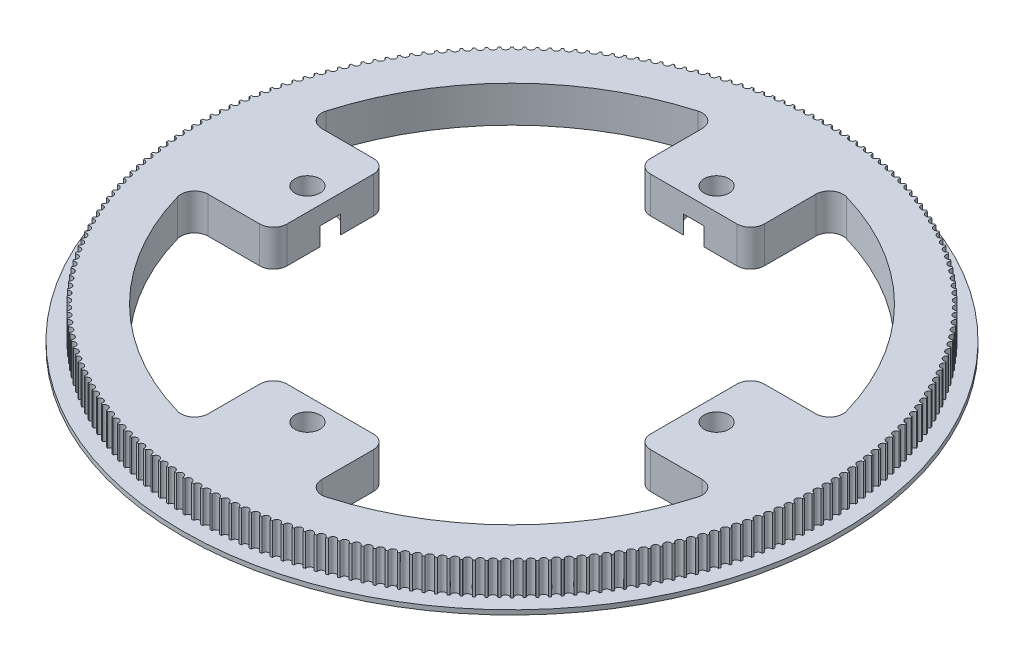
SolidWorks part; units mm, degrees
material "ABS"
ref_plane "Front Plane" through (0, 0, 0) normal (0, 0, 1) x (1, 0, 0)
ref_plane "Top Plane" through (0, 0, 0) normal (0, 1, 0) x (1, 0, 0)
ref_plane "Right Plane" through (0, 0, 0) normal (1, 0, 0) x (0, 0, -1)
sketch "Sketch1" plane through (0, 0, 0) normal (0, 1, 0) x (1, 0, 0)
  arc A0 (-0.76, 69.2508) -> (-1.2179, 69.2443) centre (0, 0) ccw
  arc A1 (-0.76, 69.2508) -> (0.76, 69.2508) centre (0, 69.255) ccw
  arc A2 (1.2179, 69.2443) -> (2.7372, 69.2009) centre (1.9776, 69.2268) ccw
  arc A3 (3.1947, 69.1813) -> (4.7122, 69.0945) centre (3.9537, 69.1421) ccw
  arc A4 (5.1689, 69.0618) -> (6.6833, 68.9318) centre (5.9265, 69.001) ccw
  arc A5 (7.139, 68.8861) -> (8.649, 68.7128) centre (7.8945, 68.8036) ccw
  arc A6 (9.1032, 68.6541) -> (10.6077, 68.4378) centre (9.856, 68.5501) ccw
  arc A7 (11.0599, 68.3662) -> (12.5577, 68.107) centre (11.8095, 68.2407) ccw
  arc A8 (13.0077, 68.0225) -> (14.4974, 67.7206) centre (13.7534, 67.8756) ccw
  arc A9 (14.9449, 67.6233) -> (16.4253, 67.279) centre (15.686, 67.4552) ccw
  arc A10 (16.8698, 67.1689) -> (18.3399, 66.7825) centre (17.6059, 66.9798) ccw
  arc A11 (18.781, 66.6598) -> (20.2394, 66.2316) centre (19.5114, 66.4497) ccw
  arc A12 (20.6769, 66.0963) -> (22.1225, 65.6266) centre (21.401, 65.8654) ccw
  arc A13 (22.5559, 65.4789) -> (23.9875, 64.9681) centre (23.2731, 65.2274) ccw
  arc A14 (24.4165, 64.8081) -> (25.8329, 64.2566) centre (25.1262, 64.5362) ccw
  arc A15 (26.2572, 64.0844) -> (27.6573, 63.4927) centre (26.9589, 63.7924) ccw
  arc A16 (28.0765, 63.3085) -> (29.4591, 62.6771) centre (28.7696, 62.9966) ccw
  arc A17 (29.8729, 62.4809) -> (31.2369, 61.8103) centre (30.5568, 62.1493) ccw
  arc A18 (31.6449, 61.6024) -> (32.9893, 60.8931) centre (32.319, 61.2514) ccw
  arc A19 (33.3912, 60.6736) -> (34.7147, 59.9262) centre (34.055, 60.3035) ccw
  arc A20 (35.1101, 59.6953) -> (36.4118, 58.9104) centre (35.7631, 59.3065) ccw
  arc A21 (36.8005, 58.6684) -> (38.0792, 57.8466) centre (37.4421, 58.261) ccw
  arc A22 (38.4608, 57.5936) -> (39.7155, 56.7356) centre (39.0905, 57.1681) ccw
  arc A23 (40.0898, 56.4718) -> (41.3195, 55.5784) centre (40.7071, 56.0285) ccw
  arc A24 (41.686, 55.304) -> (42.8897, 54.3758) centre (42.2904, 54.8432) ccw
  arc A25 (43.2483, 54.091) -> (44.425, 53.1289) centre (43.8393, 53.6132) ccw
  arc A26 (44.7753, 52.834) -> (45.924, 51.8386) centre (45.3524, 52.3394) ccw
  arc A27 (46.2658, 51.5338) -> (47.3856, 50.5061) centre (46.8285, 51.023) ccw
  arc A28 (47.7185, 50.1916) -> (48.8085, 49.1323) centre (48.2664, 49.665) ccw
  arc A29 (49.1323, 48.8085) -> (50.1916, 47.7185) centre (49.665, 48.2664) ccw
  arc A30 (50.5061, 47.3856) -> (51.5338, 46.2658) centre (51.023, 46.8285) ccw
  arc A31 (51.8386, 45.924) -> (52.834, 44.7753) centre (52.3394, 45.3524) ccw
  arc A32 (53.1289, 44.425) -> (54.091, 43.2483) centre (53.6132, 43.8393) ccw
  arc A33 (54.3758, 42.8897) -> (55.304, 41.686) centre (54.8432, 42.2904) ccw
  arc A34 (55.5784, 41.3195) -> (56.4718, 40.0898) centre (56.0285, 40.7071) ccw
  arc A35 (56.7356, 39.7155) -> (57.5936, 38.4608) centre (57.1681, 39.0905) ccw
  arc A36 (57.8466, 38.0792) -> (58.6684, 36.8005) centre (58.261, 37.4421) ccw
  arc A37 (58.9104, 36.4118) -> (59.6953, 35.1101) centre (59.3065, 35.7631) ccw
  arc A38 (59.9262, 34.7147) -> (60.6736, 33.3912) centre (60.3035, 34.055) ccw
  arc A39 (60.8931, 32.9893) -> (61.6024, 31.6449) centre (61.2514, 32.319) ccw
  arc A40 (61.8103, 31.2369) -> (62.4809, 29.8729) centre (62.1493, 30.5568) ccw
  arc A41 (62.6771, 29.4591) -> (63.3085, 28.0765) centre (62.9966, 28.7696) ccw
  arc A42 (63.4927, 27.6573) -> (64.0844, 26.2572) centre (63.7924, 26.9589) ccw
  arc A43 (64.2566, 25.8329) -> (64.8081, 24.4165) centre (64.5362, 25.1262) ccw
  arc A44 (64.9681, 23.9875) -> (65.4789, 22.5559) centre (65.2274, 23.2731) ccw
  arc A45 (65.6266, 22.1225) -> (66.0963, 20.6769) centre (65.8654, 21.401) ccw
  arc A46 (66.2316, 20.2394) -> (66.6598, 18.781) centre (66.4497, 19.5114) ccw
  arc A47 (66.7825, 18.3399) -> (67.1689, 16.8698) centre (66.9798, 17.6059) ccw
  arc A48 (67.279, 16.4253) -> (67.6233, 14.9449) centre (67.4552, 15.686) ccw
  arc A49 (67.7206, 14.4974) -> (68.0225, 13.0077) centre (67.8756, 13.7534) ccw
  arc A50 (68.107, 12.5577) -> (68.3662, 11.0599) centre (68.2407, 11.8095) ccw
  arc A51 (68.4378, 10.6077) -> (68.6541, 9.1032) centre (68.5501, 9.856) ccw
  arc A52 (68.7128, 8.649) -> (68.8861, 7.139) centre (68.8036, 7.8945) ccw
  arc A53 (68.9318, 6.6833) -> (69.0618, 5.1689) centre (69.001, 5.9265) ccw
  arc A54 (69.0945, 4.7122) -> (69.1813, 3.1947) centre (69.1421, 3.9537) ccw
  arc A55 (69.2009, 2.7372) -> (69.2443, 1.2179) centre (69.2268, 1.9776) ccw
  arc A56 (69.2508, 0.76) -> (69.2508, -0.76) centre (69.255, 0) ccw
  arc A57 (69.2443, -1.2179) -> (69.2009, -2.7372) centre (69.2268, -1.9776) ccw
  arc A58 (69.1813, -3.1947) -> (69.0945, -4.7122) centre (69.1421, -3.9537) ccw
  arc A59 (69.0618, -5.1689) -> (68.9318, -6.6833) centre (69.001, -5.9265) ccw
  arc A60 (68.8861, -7.139) -> (68.7128, -8.649) centre (68.8036, -7.8945) ccw
  arc A61 (68.6541, -9.1032) -> (68.4378, -10.6077) centre (68.5501, -9.856) ccw
  arc A62 (68.3662, -11.0599) -> (68.107, -12.5577) centre (68.2407, -11.8095) ccw
  arc A63 (68.0225, -13.0077) -> (67.7206, -14.4974) centre (67.8756, -13.7534) ccw
  arc A64 (67.6233, -14.9449) -> (67.279, -16.4253) centre (67.4552, -15.686) ccw
  arc A65 (67.1689, -16.8698) -> (66.7825, -18.3399) centre (66.9798, -17.6059) ccw
  arc A66 (66.6598, -18.781) -> (66.2316, -20.2394) centre (66.4497, -19.5114) ccw
  arc A67 (66.0963, -20.6769) -> (65.6266, -22.1225) centre (65.8654, -21.401) ccw
  arc A68 (65.4789, -22.5559) -> (64.9681, -23.9875) centre (65.2274, -23.2731) ccw
  arc A69 (64.8081, -24.4165) -> (64.2566, -25.8329) centre (64.5362, -25.1262) ccw
  arc A70 (64.0844, -26.2572) -> (63.4927, -27.6573) centre (63.7924, -26.9589) ccw
  arc A71 (63.3085, -28.0765) -> (62.6771, -29.4591) centre (62.9966, -28.7696) ccw
  arc A72 (62.4809, -29.8729) -> (61.8103, -31.2369) centre (62.1493, -30.5568) ccw
  arc A73 (61.6024, -31.6449) -> (60.8931, -32.9893) centre (61.2514, -32.319) ccw
  arc A74 (60.6736, -33.3912) -> (59.9262, -34.7147) centre (60.3035, -34.055) ccw
  arc A75 (59.6953, -35.1101) -> (58.9104, -36.4118) centre (59.3065, -35.7631) ccw
  arc A76 (58.6684, -36.8005) -> (57.8466, -38.0792) centre (58.261, -37.4421) ccw
  arc A77 (57.5936, -38.4608) -> (56.7356, -39.7155) centre (57.1681, -39.0905) ccw
  arc A78 (56.4718, -40.0898) -> (55.5784, -41.3195) centre (56.0285, -40.7071) ccw
  arc A79 (55.304, -41.686) -> (54.3758, -42.8897) centre (54.8432, -42.2904) ccw
  arc A80 (54.091, -43.2483) -> (53.1289, -44.425) centre (53.6132, -43.8393) ccw
  arc A81 (52.834, -44.7753) -> (51.8386, -45.924) centre (52.3394, -45.3524) ccw
  arc A82 (51.5338, -46.2658) -> (50.5061, -47.3856) centre (51.023, -46.8285) ccw
  arc A83 (50.1916, -47.7185) -> (49.1323, -48.8085) centre (49.665, -48.2664) ccw
  arc A84 (48.8085, -49.1323) -> (47.7185, -50.1916) centre (48.2664, -49.665) ccw
  arc A85 (47.3856, -50.5061) -> (46.2658, -51.5338) centre (46.8285, -51.023) ccw
  arc A86 (45.924, -51.8386) -> (44.7753, -52.834) centre (45.3524, -52.3394) ccw
  arc A87 (44.425, -53.1289) -> (43.2483, -54.091) centre (43.8393, -53.6132) ccw
  arc A88 (42.8897, -54.3758) -> (41.686, -55.304) centre (42.2904, -54.8432) ccw
  arc A89 (41.3195, -55.5784) -> (40.0898, -56.4718) centre (40.7071, -56.0285) ccw
  arc A90 (39.7155, -56.7356) -> (38.4608, -57.5936) centre (39.0905, -57.1681) ccw
  arc A91 (38.0792, -57.8466) -> (36.8005, -58.6684) centre (37.4421, -58.261) ccw
  arc A92 (36.4118, -58.9104) -> (35.1101, -59.6953) centre (35.7631, -59.3065) ccw
  arc A93 (34.7147, -59.9262) -> (33.3912, -60.6736) centre (34.055, -60.3035) ccw
  arc A94 (32.9893, -60.8931) -> (31.6449, -61.6024) centre (32.319, -61.2514) ccw
  arc A95 (31.2369, -61.8103) -> (29.8729, -62.4809) centre (30.5568, -62.1493) ccw
  arc A96 (29.4591, -62.6771) -> (28.0765, -63.3085) centre (28.7696, -62.9966) ccw
  arc A97 (27.6573, -63.4927) -> (26.2572, -64.0844) centre (26.9589, -63.7924) ccw
  arc A98 (25.8329, -64.2566) -> (24.4165, -64.8081) centre (25.1262, -64.5362) ccw
  arc A99 (23.9875, -64.9681) -> (22.5559, -65.4789) centre (23.2731, -65.2274) ccw
  arc A100 (22.1225, -65.6266) -> (20.6769, -66.0963) centre (21.401, -65.8654) ccw
  arc A101 (20.2394, -66.2316) -> (18.781, -66.6598) centre (19.5114, -66.4497) ccw
  arc A102 (18.3399, -66.7825) -> (16.8698, -67.1689) centre (17.6059, -66.9798) ccw
  arc A103 (16.4253, -67.279) -> (14.9449, -67.6233) centre (15.686, -67.4552) ccw
  arc A104 (14.4974, -67.7206) -> (13.0077, -68.0225) centre (13.7534, -67.8756) ccw
  arc A105 (12.5577, -68.107) -> (11.0599, -68.3662) centre (11.8095, -68.2407) ccw
  arc A106 (10.6077, -68.4378) -> (9.1032, -68.6541) centre (9.856, -68.5501) ccw
  arc A107 (8.649, -68.7128) -> (7.139, -68.8861) centre (7.8945, -68.8036) ccw
  arc A108 (6.6833, -68.9318) -> (5.1689, -69.0618) centre (5.9265, -69.001) ccw
  arc A109 (4.7122, -69.0945) -> (3.1947, -69.1813) centre (3.9537, -69.1421) ccw
  arc A110 (2.7372, -69.2009) -> (1.2179, -69.2443) centre (1.9776, -69.2268) ccw
  arc A111 (0.76, -69.2508) -> (-0.76, -69.2508) centre (0, -69.255) ccw
  arc A112 (-1.2179, -69.2443) -> (-2.7372, -69.2009) centre (-1.9776, -69.2268) ccw
  arc A113 (-3.1947, -69.1813) -> (-4.7122, -69.0945) centre (-3.9537, -69.1421) ccw
  arc A114 (-5.1689, -69.0618) -> (-6.6833, -68.9318) centre (-5.9265, -69.001) ccw
  arc A115 (-7.139, -68.8861) -> (-8.649, -68.7128) centre (-7.8945, -68.8036) ccw
  arc A116 (-9.1032, -68.6541) -> (-10.6077, -68.4378) centre (-9.856, -68.5501) ccw
  arc A117 (-11.0599, -68.3662) -> (-12.5577, -68.107) centre (-11.8095, -68.2407) ccw
  arc A118 (-13.0077, -68.0225) -> (-14.4974, -67.7206) centre (-13.7534, -67.8756) ccw
  arc A119 (-14.9449, -67.6233) -> (-16.4253, -67.279) centre (-15.686, -67.4552) ccw
  arc A120 (-16.8698, -67.1689) -> (-18.3399, -66.7825) centre (-17.6059, -66.9798) ccw
  arc A121 (-18.781, -66.6598) -> (-20.2394, -66.2316) centre (-19.5114, -66.4497) ccw
  arc A122 (-20.6769, -66.0963) -> (-22.1225, -65.6266) centre (-21.401, -65.8654) ccw
  arc A123 (-22.5559, -65.4789) -> (-23.9875, -64.9681) centre (-23.2731, -65.2274) ccw
  arc A124 (-24.4165, -64.8081) -> (-25.8329, -64.2566) centre (-25.1262, -64.5362) ccw
  arc A125 (-26.2572, -64.0844) -> (-27.6573, -63.4927) centre (-26.9589, -63.7924) ccw
  arc A126 (-28.0765, -63.3085) -> (-29.4591, -62.6771) centre (-28.7696, -62.9966) ccw
  arc A127 (-29.8729, -62.4809) -> (-31.2369, -61.8103) centre (-30.5568, -62.1493) ccw
  arc A128 (-31.6449, -61.6024) -> (-32.9893, -60.8931) centre (-32.319, -61.2514) ccw
  arc A129 (-33.3912, -60.6736) -> (-34.7147, -59.9262) centre (-34.055, -60.3035) ccw
  arc A130 (-35.1101, -59.6953) -> (-36.4118, -58.9104) centre (-35.7631, -59.3065) ccw
  arc A131 (-36.8005, -58.6684) -> (-38.0792, -57.8466) centre (-37.4421, -58.261) ccw
  arc A132 (-38.4608, -57.5936) -> (-39.7155, -56.7356) centre (-39.0905, -57.1681) ccw
  arc A133 (-40.0898, -56.4718) -> (-41.3195, -55.5784) centre (-40.7071, -56.0285) ccw
  arc A134 (-41.686, -55.304) -> (-42.8897, -54.3758) centre (-42.2904, -54.8432) ccw
  arc A135 (-43.2483, -54.091) -> (-44.425, -53.1289) centre (-43.8393, -53.6132) ccw
  arc A136 (-44.7753, -52.834) -> (-45.924, -51.8386) centre (-45.3524, -52.3394) ccw
  arc A137 (-46.2658, -51.5338) -> (-47.3856, -50.5061) centre (-46.8285, -51.023) ccw
  arc A138 (-47.7185, -50.1916) -> (-48.8085, -49.1323) centre (-48.2664, -49.665) ccw
  arc A139 (-49.1323, -48.8085) -> (-50.1916, -47.7185) centre (-49.665, -48.2664) ccw
  arc A140 (-50.5061, -47.3856) -> (-51.5338, -46.2658) centre (-51.023, -46.8285) ccw
  arc A141 (-51.8386, -45.924) -> (-52.834, -44.7753) centre (-52.3394, -45.3524) ccw
  arc A142 (-53.1289, -44.425) -> (-54.091, -43.2483) centre (-53.6132, -43.8393) ccw
  arc A143 (-54.3758, -42.8897) -> (-55.304, -41.686) centre (-54.8432, -42.2904) ccw
  arc A144 (-55.5784, -41.3195) -> (-56.4718, -40.0898) centre (-56.0285, -40.7071) ccw
  arc A145 (-56.7356, -39.7155) -> (-57.5936, -38.4608) centre (-57.1681, -39.0905) ccw
  arc A146 (-57.8466, -38.0792) -> (-58.6684, -36.8005) centre (-58.261, -37.4421) ccw
  arc A147 (-58.9104, -36.4118) -> (-59.6953, -35.1101) centre (-59.3065, -35.7631) ccw
  arc A148 (-59.9262, -34.7147) -> (-60.6736, -33.3912) centre (-60.3035, -34.055) ccw
  arc A149 (-60.8931, -32.9893) -> (-61.6024, -31.6449) centre (-61.2514, -32.319) ccw
  arc A150 (-61.8103, -31.2369) -> (-62.4809, -29.8729) centre (-62.1493, -30.5568) ccw
  arc A151 (-62.6771, -29.4591) -> (-63.3085, -28.0765) centre (-62.9966, -28.7696) ccw
  arc A152 (-63.4927, -27.6573) -> (-64.0844, -26.2572) centre (-63.7924, -26.9589) ccw
  arc A153 (-64.2566, -25.8329) -> (-64.8081, -24.4165) centre (-64.5362, -25.1262) ccw
  arc A154 (-64.9681, -23.9875) -> (-65.4789, -22.5559) centre (-65.2274, -23.2731) ccw
  arc A155 (-65.6266, -22.1225) -> (-66.0963, -20.6769) centre (-65.8654, -21.401) ccw
  arc A156 (-66.2316, -20.2394) -> (-66.6598, -18.781) centre (-66.4497, -19.5114) ccw
  arc A157 (-66.7825, -18.3399) -> (-67.1689, -16.8698) centre (-66.9798, -17.6059) ccw
  arc A158 (-67.279, -16.4253) -> (-67.6233, -14.9449) centre (-67.4552, -15.686) ccw
  arc A159 (-67.7206, -14.4974) -> (-68.0225, -13.0077) centre (-67.8756, -13.7534) ccw
  arc A160 (-68.107, -12.5577) -> (-68.3662, -11.0599) centre (-68.2407, -11.8095) ccw
  arc A161 (-68.4378, -10.6077) -> (-68.6541, -9.1032) centre (-68.5501, -9.856) ccw
  arc A162 (-68.7128, -8.649) -> (-68.8861, -7.139) centre (-68.8036, -7.8945) ccw
  arc A163 (-68.9318, -6.6833) -> (-69.0618, -5.1689) centre (-69.001, -5.9265) ccw
  arc A164 (-69.0945, -4.7122) -> (-69.1813, -3.1947) centre (-69.1421, -3.9537) ccw
  arc A165 (-69.2009, -2.7372) -> (-69.2443, -1.2179) centre (-69.2268, -1.9776) ccw
  arc A166 (-69.2508, -0.76) -> (-69.2508, 0.76) centre (-69.255, 0) ccw
  arc A167 (-69.2443, 1.2179) -> (-69.2009, 2.7372) centre (-69.2268, 1.9776) ccw
  arc A168 (-69.1813, 3.1947) -> (-69.0945, 4.7122) centre (-69.1421, 3.9537) ccw
  arc A169 (-69.0618, 5.1689) -> (-68.9318, 6.6833) centre (-69.001, 5.9265) ccw
  arc A170 (-68.8861, 7.139) -> (-68.7128, 8.649) centre (-68.8036, 7.8945) ccw
  arc A171 (-68.6541, 9.1032) -> (-68.4378, 10.6077) centre (-68.5501, 9.856) ccw
  arc A172 (-68.3662, 11.0599) -> (-68.107, 12.5577) centre (-68.2407, 11.8095) ccw
  arc A173 (-68.0225, 13.0077) -> (-67.7206, 14.4974) centre (-67.8756, 13.7534) ccw
  arc A174 (-67.6233, 14.9449) -> (-67.279, 16.4253) centre (-67.4552, 15.686) ccw
  arc A175 (-67.1689, 16.8698) -> (-66.7825, 18.3399) centre (-66.9798, 17.6059) ccw
  arc A176 (-66.6598, 18.781) -> (-66.2316, 20.2394) centre (-66.4497, 19.5114) ccw
  arc A177 (-66.0963, 20.6769) -> (-65.6266, 22.1225) centre (-65.8654, 21.401) ccw
  arc A178 (-65.4789, 22.5559) -> (-64.9681, 23.9875) centre (-65.2274, 23.2731) ccw
  arc A179 (-64.8081, 24.4165) -> (-64.2566, 25.8329) centre (-64.5362, 25.1262) ccw
  arc A180 (-64.0844, 26.2572) -> (-63.4927, 27.6573) centre (-63.7924, 26.9589) ccw
  arc A181 (-63.3085, 28.0765) -> (-62.6771, 29.4591) centre (-62.9966, 28.7696) ccw
  arc A182 (-62.4809, 29.8729) -> (-61.8103, 31.2369) centre (-62.1493, 30.5568) ccw
  arc A183 (-61.6024, 31.6449) -> (-60.8931, 32.9893) centre (-61.2514, 32.319) ccw
  arc A184 (-60.6736, 33.3912) -> (-59.9262, 34.7147) centre (-60.3035, 34.055) ccw
  arc A185 (-59.6953, 35.1101) -> (-58.9104, 36.4118) centre (-59.3065, 35.7631) ccw
  arc A186 (-58.6684, 36.8005) -> (-57.8466, 38.0792) centre (-58.261, 37.4421) ccw
  arc A187 (-57.5936, 38.4608) -> (-56.7356, 39.7155) centre (-57.1681, 39.0905) ccw
  arc A188 (-56.4718, 40.0898) -> (-55.5784, 41.3195) centre (-56.0285, 40.7071) ccw
  arc A189 (-55.304, 41.686) -> (-54.3758, 42.8897) centre (-54.8432, 42.2904) ccw
  arc A190 (-54.091, 43.2483) -> (-53.1289, 44.425) centre (-53.6132, 43.8393) ccw
  arc A191 (-52.834, 44.7753) -> (-51.8386, 45.924) centre (-52.3394, 45.3524) ccw
  arc A192 (-51.5338, 46.2658) -> (-50.5061, 47.3856) centre (-51.023, 46.8285) ccw
  arc A193 (-50.1916, 47.7185) -> (-49.1323, 48.8085) centre (-49.665, 48.2664) ccw
  arc A194 (-48.8085, 49.1323) -> (-47.7185, 50.1916) centre (-48.2664, 49.665) ccw
  arc A195 (-47.3856, 50.5061) -> (-46.2658, 51.5338) centre (-46.8285, 51.023) ccw
  arc A196 (-45.924, 51.8386) -> (-44.7753, 52.834) centre (-45.3524, 52.3394) ccw
  arc A197 (-44.425, 53.1289) -> (-43.2483, 54.091) centre (-43.8393, 53.6132) ccw
  arc A198 (-42.8897, 54.3758) -> (-41.686, 55.304) centre (-42.2904, 54.8432) ccw
  arc A199 (-41.3195, 55.5784) -> (-40.0898, 56.4718) centre (-40.7071, 56.0285) ccw
  arc A200 (-39.7155, 56.7356) -> (-38.4608, 57.5936) centre (-39.0905, 57.1681) ccw
  arc A201 (-38.0792, 57.8466) -> (-36.8005, 58.6684) centre (-37.4421, 58.261) ccw
  arc A202 (-36.4118, 58.9104) -> (-35.1101, 59.6953) centre (-35.7631, 59.3065) ccw
  arc A203 (-34.7147, 59.9262) -> (-33.3912, 60.6736) centre (-34.055, 60.3035) ccw
  arc A204 (-32.9893, 60.8931) -> (-31.6449, 61.6024) centre (-32.319, 61.2514) ccw
  arc A205 (-31.2369, 61.8103) -> (-29.8729, 62.4809) centre (-30.5568, 62.1493) ccw
  arc A206 (-29.4591, 62.6771) -> (-28.0765, 63.3085) centre (-28.7696, 62.9966) ccw
  arc A207 (-27.6573, 63.4927) -> (-26.2572, 64.0844) centre (-26.9589, 63.7924) ccw
  arc A208 (-25.8329, 64.2566) -> (-24.4165, 64.8081) centre (-25.1262, 64.5362) ccw
  arc A209 (-23.9875, 64.9681) -> (-22.5559, 65.4789) centre (-23.2731, 65.2274) ccw
  arc A210 (-22.1225, 65.6266) -> (-20.6769, 66.0963) centre (-21.401, 65.8654) ccw
  arc A211 (-20.2394, 66.2316) -> (-18.781, 66.6598) centre (-19.5114, 66.4497) ccw
  arc A212 (-18.3399, 66.7825) -> (-16.8698, 67.1689) centre (-17.6059, 66.9798) ccw
  arc A213 (-16.4253, 67.279) -> (-14.9449, 67.6233) centre (-15.686, 67.4552) ccw
  arc A214 (-14.4974, 67.7206) -> (-13.0077, 68.0225) centre (-13.7534, 67.8756) ccw
  arc A215 (-12.5577, 68.107) -> (-11.0599, 68.3662) centre (-11.8095, 68.2407) ccw
  arc A216 (-10.6077, 68.4378) -> (-9.1032, 68.6541) centre (-9.856, 68.5501) ccw
  arc A217 (-8.649, 68.7128) -> (-7.139, 68.8861) centre (-7.8945, 68.8036) ccw
  arc A218 (-6.6833, 68.9318) -> (-5.1689, 69.0618) centre (-5.9265, 69.001) ccw
  arc A219 (-4.7122, 69.0945) -> (-3.1947, 69.1813) centre (-3.9537, 69.1421) ccw
  arc A220 (-2.7372, 69.2009) -> (-1.2179, 69.2443) centre (-1.9776, 69.2268) ccw
  arc A221 (1.2179, 69.2443) -> (0.76, 69.2508) centre (0, 0) ccw
  arc A222 (3.1947, 69.1813) -> (2.7372, 69.2009) centre (0, 0) ccw
  arc A223 (5.1689, 69.0618) -> (4.7122, 69.0945) centre (0, 0) ccw
  arc A224 (7.139, 68.8861) -> (6.6833, 68.9318) centre (0, 0) ccw
  arc A225 (9.1032, 68.6541) -> (8.649, 68.7128) centre (0, 0) ccw
  arc A226 (11.0599, 68.3662) -> (10.6077, 68.4378) centre (0, 0) ccw
  arc A227 (13.0077, 68.0225) -> (12.5577, 68.107) centre (0, 0) ccw
  arc A228 (14.9449, 67.6233) -> (14.4974, 67.7206) centre (0, 0) ccw
  arc A229 (16.8698, 67.1689) -> (16.4253, 67.279) centre (0, 0) ccw
  arc A230 (18.781, 66.6598) -> (18.3399, 66.7825) centre (0, 0) ccw
  arc A231 (20.6769, 66.0963) -> (20.2394, 66.2316) centre (0, 0) ccw
  arc A232 (22.5559, 65.4789) -> (22.1225, 65.6266) centre (0, 0) ccw
  arc A233 (24.4165, 64.8081) -> (23.9875, 64.9681) centre (0, 0) ccw
  arc A234 (26.2572, 64.0844) -> (25.8329, 64.2566) centre (0, 0) ccw
  arc A235 (28.0765, 63.3085) -> (27.6573, 63.4927) centre (0, 0) ccw
  arc A236 (29.8729, 62.4809) -> (29.4591, 62.6771) centre (0, 0) ccw
  arc A237 (31.6449, 61.6024) -> (31.2369, 61.8103) centre (0, 0) ccw
  arc A238 (33.3912, 60.6736) -> (32.9893, 60.8931) centre (0, 0) ccw
  arc A239 (35.1101, 59.6953) -> (34.7147, 59.9262) centre (0, 0) ccw
  arc A240 (36.8005, 58.6684) -> (36.4118, 58.9104) centre (0, 0) ccw
  arc A241 (38.4608, 57.5936) -> (38.0792, 57.8466) centre (0, 0) ccw
  arc A242 (40.0898, 56.4718) -> (39.7155, 56.7356) centre (0, 0) ccw
  arc A243 (41.686, 55.304) -> (41.3195, 55.5784) centre (0, 0) ccw
  arc A244 (43.2483, 54.091) -> (42.8897, 54.3758) centre (0, 0) ccw
  arc A245 (44.7753, 52.834) -> (44.425, 53.1289) centre (0, 0) ccw
  arc A246 (46.2658, 51.5338) -> (45.924, 51.8386) centre (0, 0) ccw
  arc A247 (47.7185, 50.1916) -> (47.3856, 50.5061) centre (0, 0) ccw
  arc A248 (49.1323, 48.8085) -> (48.8085, 49.1323) centre (0, 0) ccw
  arc A249 (50.5061, 47.3856) -> (50.1916, 47.7185) centre (0, 0) ccw
  arc A250 (51.8386, 45.924) -> (51.5338, 46.2658) centre (0, 0) ccw
  arc A251 (53.1289, 44.425) -> (52.834, 44.7753) centre (0, 0) ccw
  arc A252 (54.3758, 42.8897) -> (54.091, 43.2483) centre (0, 0) ccw
  arc A253 (55.5784, 41.3195) -> (55.304, 41.686) centre (0, 0) ccw
  arc A254 (56.7356, 39.7155) -> (56.4718, 40.0898) centre (0, 0) ccw
  arc A255 (57.8466, 38.0792) -> (57.5936, 38.4608) centre (0, 0) ccw
  arc A256 (58.9104, 36.4118) -> (58.6684, 36.8005) centre (0, 0) ccw
  arc A257 (59.9262, 34.7147) -> (59.6953, 35.1101) centre (0, 0) ccw
  arc A258 (60.8931, 32.9893) -> (60.6736, 33.3912) centre (0, 0) ccw
  arc A259 (61.8103, 31.2369) -> (61.6024, 31.6449) centre (0, 0) ccw
  arc A260 (62.6771, 29.4591) -> (62.4809, 29.8729) centre (0, 0) ccw
  arc A261 (63.4927, 27.6573) -> (63.3085, 28.0765) centre (0, 0) ccw
  arc A262 (64.2566, 25.8329) -> (64.0844, 26.2572) centre (0, 0) ccw
  arc A263 (64.9681, 23.9875) -> (64.8081, 24.4165) centre (0, 0) ccw
  arc A264 (65.6266, 22.1225) -> (65.4789, 22.5559) centre (0, 0) ccw
  arc A265 (66.2316, 20.2394) -> (66.0963, 20.6769) centre (0, 0) ccw
  arc A266 (66.7825, 18.3399) -> (66.6598, 18.781) centre (0, 0) ccw
  arc A267 (67.279, 16.4253) -> (67.1689, 16.8698) centre (0, 0) ccw
  arc A268 (67.7206, 14.4974) -> (67.6233, 14.9449) centre (0, 0) ccw
  arc A269 (68.107, 12.5577) -> (68.0225, 13.0077) centre (0, 0) ccw
  arc A270 (68.4378, 10.6077) -> (68.3662, 11.0599) centre (0, 0) ccw
  arc A271 (68.7128, 8.649) -> (68.6541, 9.1032) centre (0, 0) ccw
  arc A272 (68.9318, 6.6833) -> (68.8861, 7.139) centre (0, 0) ccw
  arc A273 (69.0945, 4.7122) -> (69.0618, 5.1689) centre (0, 0) ccw
  arc A274 (69.2009, 2.7372) -> (69.1813, 3.1947) centre (0, 0) ccw
  arc A275 (69.2508, 0.76) -> (69.2443, 1.2179) centre (0, 0) ccw
  arc A276 (69.2443, -1.2179) -> (69.2508, -0.76) centre (0, 0) ccw
  arc A277 (69.1813, -3.1947) -> (69.2009, -2.7372) centre (0, 0) ccw
  arc A278 (69.0618, -5.1689) -> (69.0945, -4.7122) centre (0, 0) ccw
  arc A279 (68.8861, -7.139) -> (68.9318, -6.6833) centre (0, 0) ccw
  arc A280 (68.6541, -9.1032) -> (68.7128, -8.649) centre (0, 0) ccw
  arc A281 (68.3662, -11.0599) -> (68.4378, -10.6077) centre (0, 0) ccw
  arc A282 (68.0225, -13.0077) -> (68.107, -12.5577) centre (0, 0) ccw
  arc A283 (67.6233, -14.9449) -> (67.7206, -14.4974) centre (0, 0) ccw
  arc A284 (67.1689, -16.8698) -> (67.279, -16.4253) centre (0, 0) ccw
  arc A285 (66.6598, -18.781) -> (66.7825, -18.3399) centre (0, 0) ccw
  arc A286 (66.0963, -20.6769) -> (66.2316, -20.2394) centre (0, 0) ccw
  arc A287 (65.4789, -22.5559) -> (65.6266, -22.1225) centre (0, 0) ccw
  arc A288 (64.8081, -24.4165) -> (64.9681, -23.9875) centre (0, 0) ccw
  arc A289 (64.0844, -26.2572) -> (64.2566, -25.8329) centre (0, 0) ccw
  arc A290 (63.3085, -28.0765) -> (63.4927, -27.6573) centre (0, 0) ccw
  arc A291 (62.4809, -29.8729) -> (62.6771, -29.4591) centre (0, 0) ccw
  arc A292 (61.6024, -31.6449) -> (61.8103, -31.2369) centre (0, 0) ccw
  arc A293 (60.6736, -33.3912) -> (60.8931, -32.9893) centre (0, 0) ccw
  arc A294 (59.6953, -35.1101) -> (59.9262, -34.7147) centre (0, 0) ccw
  arc A295 (58.6684, -36.8005) -> (58.9104, -36.4118) centre (0, 0) ccw
  arc A296 (57.5936, -38.4608) -> (57.8466, -38.0792) centre (0, 0) ccw
  arc A297 (56.4718, -40.0898) -> (56.7356, -39.7155) centre (0, 0) ccw
  arc A298 (55.304, -41.686) -> (55.5784, -41.3195) centre (0, 0) ccw
  arc A299 (54.091, -43.2483) -> (54.3758, -42.8897) centre (0, 0) ccw
  arc A300 (52.834, -44.7753) -> (53.1289, -44.425) centre (0, 0) ccw
  arc A301 (51.5338, -46.2658) -> (51.8386, -45.924) centre (0, 0) ccw
  arc A302 (50.1916, -47.7185) -> (50.5061, -47.3856) centre (0, 0) ccw
  arc A303 (48.8085, -49.1323) -> (49.1323, -48.8085) centre (0, 0) ccw
  arc A304 (47.3856, -50.5061) -> (47.7185, -50.1916) centre (0, 0) ccw
  arc A305 (45.924, -51.8386) -> (46.2658, -51.5338) centre (0, 0) ccw
  arc A306 (44.425, -53.1289) -> (44.7753, -52.834) centre (0, 0) ccw
  arc A307 (42.8897, -54.3758) -> (43.2483, -54.091) centre (0, 0) ccw
  arc A308 (41.3195, -55.5784) -> (41.686, -55.304) centre (0, 0) ccw
  arc A309 (39.7155, -56.7356) -> (40.0898, -56.4718) centre (0, 0) ccw
  arc A310 (38.0792, -57.8466) -> (38.4608, -57.5936) centre (0, 0) ccw
  arc A311 (36.4118, -58.9104) -> (36.8005, -58.6684) centre (0, 0) ccw
  arc A312 (34.7147, -59.9262) -> (35.1101, -59.6953) centre (0, 0) ccw
  arc A313 (32.9893, -60.8931) -> (33.3912, -60.6736) centre (0, 0) ccw
  arc A314 (31.2369, -61.8103) -> (31.6449, -61.6024) centre (0, 0) ccw
  arc A315 (29.4591, -62.6771) -> (29.8729, -62.4809) centre (0, 0) ccw
  arc A316 (27.6573, -63.4927) -> (28.0765, -63.3085) centre (0, 0) ccw
  arc A317 (23.9875, -64.9681) -> (24.4165, -64.8081) centre (0, 0) ccw
  arc A318 (25.8329, -64.2566) -> (26.2572, -64.0844) centre (0, 0) ccw
  arc A319 (22.1225, -65.6266) -> (22.5559, -65.4789) centre (0, 0) ccw
  arc A320 (20.2394, -66.2316) -> (20.6769, -66.0963) centre (0, 0) ccw
  arc A321 (18.3399, -66.7825) -> (18.781, -66.6598) centre (0, 0) ccw
  arc A322 (16.4253, -67.279) -> (16.8698, -67.1689) centre (0, 0) ccw
  arc A323 (14.4974, -67.7206) -> (14.9449, -67.6233) centre (0, 0) ccw
  arc A324 (12.5577, -68.107) -> (13.0077, -68.0225) centre (0, 0) ccw
  arc A325 (10.6077, -68.4378) -> (11.0599, -68.3662) centre (0, 0) ccw
  arc A326 (8.649, -68.7128) -> (9.1032, -68.6541) centre (0, 0) ccw
  arc A327 (6.6833, -68.9318) -> (7.139, -68.8861) centre (0, 0) ccw
  arc A328 (4.7122, -69.0945) -> (5.1689, -69.0618) centre (0, 0) ccw
  arc A329 (2.7372, -69.2009) -> (3.1947, -69.1813) centre (0, 0) ccw
  arc A330 (0.76, -69.2508) -> (1.2179, -69.2443) centre (0, 0) ccw
  arc A331 (-1.2179, -69.2443) -> (-0.76, -69.2508) centre (0, 0) ccw
  arc A332 (-3.1947, -69.1813) -> (-2.7372, -69.2009) centre (0, 0) ccw
  arc A333 (-5.1689, -69.0618) -> (-4.7122, -69.0945) centre (0, 0) ccw
  arc A334 (-7.139, -68.8861) -> (-6.6833, -68.9318) centre (0, 0) ccw
  arc A335 (-9.1032, -68.6541) -> (-8.649, -68.7128) centre (0, 0) ccw
  arc A336 (-11.0599, -68.3662) -> (-10.6077, -68.4378) centre (0, 0) ccw
  arc A337 (-13.0077, -68.0225) -> (-12.5577, -68.107) centre (0, 0) ccw
  arc A338 (-14.9449, -67.6233) -> (-14.4974, -67.7206) centre (0, 0) ccw
  arc A339 (-16.8698, -67.1689) -> (-16.4253, -67.279) centre (0, 0) ccw
  arc A340 (-18.781, -66.6598) -> (-18.3399, -66.7825) centre (0, 0) ccw
  arc A341 (-20.6769, -66.0963) -> (-20.2394, -66.2316) centre (0, 0) ccw
  arc A342 (-22.5559, -65.4789) -> (-22.1225, -65.6266) centre (0, 0) ccw
  arc A343 (-24.4165, -64.8081) -> (-23.9875, -64.9681) centre (0, 0) ccw
  arc A344 (-26.2572, -64.0844) -> (-25.8329, -64.2566) centre (0, 0) ccw
  arc A345 (-28.0765, -63.3085) -> (-27.6573, -63.4927) centre (0, 0) ccw
  arc A346 (-29.8729, -62.4809) -> (-29.4591, -62.6771) centre (0, 0) ccw
  arc A347 (-31.6449, -61.6024) -> (-31.2369, -61.8103) centre (0, 0) ccw
  arc A348 (-33.3912, -60.6736) -> (-32.9893, -60.8931) centre (0, 0) ccw
  arc A349 (-35.1101, -59.6953) -> (-34.7147, -59.9262) centre (0, 0) ccw
  arc A350 (-36.8005, -58.6684) -> (-36.4118, -58.9104) centre (0, 0) ccw
  arc A351 (-38.4608, -57.5936) -> (-38.0792, -57.8466) centre (0, 0) ccw
  arc A352 (-40.0898, -56.4718) -> (-39.7155, -56.7356) centre (0, 0) ccw
  arc A353 (-41.686, -55.304) -> (-41.3195, -55.5784) centre (0, 0) ccw
  arc A354 (-43.2483, -54.091) -> (-42.8897, -54.3758) centre (0, 0) ccw
  arc A355 (-44.7753, -52.834) -> (-44.425, -53.1289) centre (0, 0) ccw
  arc A356 (-46.2658, -51.5338) -> (-45.924, -51.8386) centre (0, 0) ccw
  arc A357 (-47.7185, -50.1916) -> (-47.3856, -50.5061) centre (0, 0) ccw
  arc A358 (-49.1323, -48.8085) -> (-48.8085, -49.1323) centre (0, 0) ccw
  arc A359 (-50.5061, -47.3856) -> (-50.1916, -47.7185) centre (0, 0) ccw
  arc A360 (-51.8386, -45.924) -> (-51.5338, -46.2658) centre (0, 0) ccw
  arc A361 (-53.1289, -44.425) -> (-52.834, -44.7753) centre (0, 0) ccw
  arc A362 (-54.3758, -42.8897) -> (-54.091, -43.2483) centre (0, 0) ccw
  arc A363 (-55.5784, -41.3195) -> (-55.304, -41.686) centre (0, 0) ccw
  arc A364 (-56.7356, -39.7155) -> (-56.4718, -40.0898) centre (0, 0) ccw
  arc A365 (-57.8466, -38.0792) -> (-57.5936, -38.4608) centre (0, 0) ccw
  arc A366 (-58.9104, -36.4118) -> (-58.6684, -36.8005) centre (0, 0) ccw
  arc A367 (-59.9262, -34.7147) -> (-59.6953, -35.1101) centre (0, 0) ccw
  arc A368 (-60.8931, -32.9893) -> (-60.6736, -33.3912) centre (0, 0) ccw
  arc A369 (-61.8103, -31.2369) -> (-61.6024, -31.6449) centre (0, 0) ccw
  arc A370 (-62.6771, -29.4591) -> (-62.4809, -29.8729) centre (0, 0) ccw
  arc A371 (-63.4927, -27.6573) -> (-63.3085, -28.0765) centre (0, 0) ccw
  arc A372 (-64.2566, -25.8329) -> (-64.0844, -26.2572) centre (0, 0) ccw
  arc A373 (-64.9681, -23.9875) -> (-64.8081, -24.4165) centre (0, 0) ccw
  arc A374 (-65.6266, -22.1225) -> (-65.4789, -22.5559) centre (0, 0) ccw
  arc A375 (-66.2316, -20.2394) -> (-66.0963, -20.6769) centre (0, 0) ccw
  arc A376 (-66.7825, -18.3399) -> (-66.6598, -18.781) centre (0, 0) ccw
  arc A377 (-67.279, -16.4253) -> (-67.1689, -16.8698) centre (0, 0) ccw
  arc A378 (-67.7206, -14.4974) -> (-67.6233, -14.9449) centre (0, 0) ccw
  arc A379 (-68.107, -12.5577) -> (-68.0225, -13.0077) centre (0, 0) ccw
  arc A380 (-68.4378, -10.6077) -> (-68.3662, -11.0599) centre (0, 0) ccw
  arc A381 (-68.7128, -8.649) -> (-68.6541, -9.1032) centre (0, 0) ccw
  arc A382 (-68.9318, -6.6833) -> (-68.8861, -7.139) centre (0, 0) ccw
  arc A383 (-69.0945, -4.7122) -> (-69.0618, -5.1689) centre (0, 0) ccw
  arc A384 (-69.2009, -2.7372) -> (-69.1813, -3.1947) centre (0, 0) ccw
  arc A385 (-69.2508, -0.76) -> (-69.2443, -1.2179) centre (0, 0) ccw
  arc A386 (-69.2443, 1.2179) -> (-69.2508, 0.76) centre (0, 0) ccw
  arc A387 (-69.1813, 3.1947) -> (-69.2009, 2.7372) centre (0, 0) ccw
  arc A388 (-69.0618, 5.1689) -> (-69.0945, 4.7122) centre (0, 0) ccw
  arc A389 (-68.8861, 7.139) -> (-68.9318, 6.6833) centre (0, 0) ccw
  arc A390 (-68.6541, 9.1032) -> (-68.7128, 8.649) centre (0, 0) ccw
  arc A391 (-68.3662, 11.0599) -> (-68.4378, 10.6077) centre (0, 0) ccw
  arc A392 (-68.0225, 13.0077) -> (-68.107, 12.5577) centre (0, 0) ccw
  arc A393 (-67.6233, 14.9449) -> (-67.7206, 14.4974) centre (0, 0) ccw
  arc A394 (-67.1689, 16.8698) -> (-67.279, 16.4253) centre (0, 0) ccw
  arc A395 (-66.6598, 18.781) -> (-66.7825, 18.3399) centre (0, 0) ccw
  arc A396 (-66.0963, 20.6769) -> (-66.2316, 20.2394) centre (0, 0) ccw
  arc A397 (-65.4789, 22.5559) -> (-65.6266, 22.1225) centre (0, 0) ccw
  arc A398 (-64.8081, 24.4165) -> (-64.9681, 23.9875) centre (0, 0) ccw
  arc A399 (-64.0844, 26.2572) -> (-64.2566, 25.8329) centre (0, 0) ccw
  arc A400 (-63.3085, 28.0765) -> (-63.4927, 27.6573) centre (0, 0) ccw
  arc A401 (-62.4809, 29.8729) -> (-62.6771, 29.4591) centre (0, 0) ccw
  arc A402 (-61.6024, 31.6449) -> (-61.8103, 31.2369) centre (0, 0) ccw
  arc A403 (-60.6736, 33.3912) -> (-60.8931, 32.9893) centre (0, 0) ccw
  arc A404 (-59.6953, 35.1101) -> (-59.9262, 34.7147) centre (0, 0) ccw
  arc A405 (-58.6684, 36.8005) -> (-58.9104, 36.4118) centre (0, 0) ccw
  arc A406 (-57.5936, 38.4608) -> (-57.8466, 38.0792) centre (0, 0) ccw
  arc A407 (-56.4718, 40.0898) -> (-56.7356, 39.7155) centre (0, 0) ccw
  arc A408 (-55.304, 41.686) -> (-55.5784, 41.3195) centre (0, 0) ccw
  arc A409 (-54.091, 43.2483) -> (-54.3758, 42.8897) centre (0, 0) ccw
  arc A410 (-52.834, 44.7753) -> (-53.1289, 44.425) centre (0, 0) ccw
  arc A411 (-51.5338, 46.2658) -> (-51.8386, 45.924) centre (0, 0) ccw
  arc A412 (-50.1916, 47.7185) -> (-50.5061, 47.3856) centre (0, 0) ccw
  arc A413 (-48.8085, 49.1323) -> (-49.1323, 48.8085) centre (0, 0) ccw
  arc A414 (-47.3856, 50.5061) -> (-47.7185, 50.1916) centre (0, 0) ccw
  arc A415 (-45.924, 51.8386) -> (-46.2658, 51.5338) centre (0, 0) ccw
  arc A416 (-42.8897, 54.3758) -> (-43.2483, 54.091) centre (0, 0) ccw
  arc A417 (-44.425, 53.1289) -> (-44.7753, 52.834) centre (0, 0) ccw
  arc A418 (-41.3195, 55.5784) -> (-41.686, 55.304) centre (0, 0) ccw
  arc A419 (-39.7155, 56.7356) -> (-40.0898, 56.4718) centre (0, 0) ccw
  arc A420 (-38.0792, 57.8466) -> (-38.4608, 57.5936) centre (0, 0) ccw
  arc A421 (-36.4118, 58.9104) -> (-36.8005, 58.6684) centre (0, 0) ccw
  arc A422 (-34.7147, 59.9262) -> (-35.1101, 59.6953) centre (0, 0) ccw
  arc A423 (-32.9893, 60.8931) -> (-33.3912, 60.6736) centre (0, 0) ccw
  arc A424 (-31.2369, 61.8103) -> (-31.6449, 61.6024) centre (0, 0) ccw
  arc A425 (-29.4591, 62.6771) -> (-29.8729, 62.4809) centre (0, 0) ccw
  arc A426 (-27.6573, 63.4927) -> (-28.0765, 63.3085) centre (0, 0) ccw
  arc A427 (-25.8329, 64.2566) -> (-26.2572, 64.0844) centre (0, 0) ccw
  arc A428 (-23.9875, 64.9681) -> (-24.4165, 64.8081) centre (0, 0) ccw
  arc A429 (-22.1225, 65.6266) -> (-22.5559, 65.4789) centre (0, 0) ccw
  arc A430 (-20.2394, 66.2316) -> (-20.6769, 66.0963) centre (0, 0) ccw
  arc A431 (-18.3399, 66.7825) -> (-18.781, 66.6598) centre (0, 0) ccw
  arc A432 (-16.4253, 67.279) -> (-16.8698, 67.1689) centre (0, 0) ccw
  arc A433 (-14.4974, 67.7206) -> (-14.9449, 67.6233) centre (0, 0) ccw
  arc A434 (-12.5577, 68.107) -> (-13.0077, 68.0225) centre (0, 0) ccw
  arc A435 (-8.649, 68.7128) -> (-9.1032, 68.6541) centre (0, 0) ccw
  arc A436 (-10.6077, 68.4378) -> (-11.0599, 68.3662) centre (0, 0) ccw
  arc A437 (-6.6833, 68.9318) -> (-7.139, 68.8861) centre (0, 0) ccw
  arc A438 (-4.7122, 69.0945) -> (-5.1689, 69.0618) centre (0, 0) ccw
  arc A439 (-2.7372, 69.2009) -> (-3.1947, 69.1813) centre (0, 0) ccw
  point P665 (0, 0)
  dimension "D1" = 138.51
  dimension "D2" = 1.52
  dimension "D3" = 220
extrude "Boss-Extrude1" add sketch "Sketch1" along normal blind 7
sketch "Sketch3" plane through (0, 0, 0) normal (0, -1, 0) x (1, 0, 0)
  circle A0 centre (0, 0) radius 72.5
extrude "Boss-Extrude3" add sketch "Sketch3" along normal blind 1
sketch "Sketch6" plane through (0, 7, 0) normal (0, 1, 0) x (1, 0, 0)
  line L0 (0, 0) -> (0, 50000) construction
  line L5 (-42.4236, 42.4236) -> (42.4292, -42.4292) construction
  line L6 (-42.4264, -42.4264) -> (42.4264, 42.4264) construction
  circle A0 centre (42.4264, 42.4264) radius 2.5
  circle A1 centre (42.4292, -42.4292) radius 2.5
  circle A2 centre (-42.4264, -42.4264) radius 2.5
  circle A3 centre (-42.4236, 42.4236) radius 2.5
  point P0 (0, 0)
  dimension "D3" = 5
  dimension "D1" = 84.85
  dimension "D2" = 84.85
  dimension "D4" = 120
  dimension "D5" = 90
  dimension "D6" = 45
extrude "Cut-Extrude3" [suppressed] cut sketch "Sketch6" against normal through all
sketch "Sketch7" plane through (0, 7, 0) normal (0, 1, 0) x (1, 0, 0)
  circle A0 centre (0, 0) radius 50
  point P27 (-0.4923, 0.4115)
  point P28 (0, 0)
  dimension "D1" = 100
extrude "Cut-Extrude4" [suppressed] cut sketch "Sketch7" against normal through all
sketch "Sketch10" plane through (0, 7, 0) normal (0, 1, 0) x (1, 0, 0)
  line L0 (-25, 43.3013) -> (-51.5261, 89.2458) construction
  line L2 (-43.3013, 25) -> (-80.9622, 46.7436) construction
  line L3 (-29.625, -51.312) -> (-25, -43.3013)
  line L4 (-43.3013, -25) -> (-51.312, -29.625)
  line L5 (25, -43.3013) -> (29.625, -51.312)
  line L6 (43.3013, -25) -> (51.312, -29.625)
  line L7 (51.312, 29.625) -> (43.3013, 25)
  line L8 (29.625, 51.312) -> (25, 43.3013)
  line L9 (-29.625, 51.312) -> (-25, 43.3013)
  line L10 (-51.312, 29.625) -> (-43.3013, 25)
  arc A0 (-29.625, -51.312) -> (29.625, -51.312) centre (0, 0) ccw
  arc A1 (51.312, -29.625) -> (51.312, 29.625) centre (0, 0) ccw
  arc A2 (29.625, 51.312) -> (-29.625, 51.312) centre (0, 0) ccw
  arc A3 (-51.312, 29.625) -> (-51.312, -29.625) centre (0, 0) ccw
  arc A4 (-25, -43.3013) -> (25, -43.3013) centre (0, 0) ccw
  arc A5 (43.3013, -25) -> (43.3013, 25) centre (0, 0) ccw
  arc A6 (25, 43.3013) -> (-25, 43.3013) centre (0, 0) ccw
  arc A7 (-43.3013, 25) -> (-43.3013, -25) centre (0, 0) ccw
  point P17 (0, 0)
extrude "Cut-Extrude5" [suppressed] cut sketch "Sketch10" against normal through all
sketch "Sketch11" plane through (0, 7, 0) normal (0, 1, 0) x (1, 0, 0)
  circle A0 centre (0, 0) radius 52.5
  dimension "D1" = 105
extrude "Cut-Extrude6" [suppressed] cut sketch "Sketch11" against normal blind 10
fillet "Fillet1" [suppressed] radius 3
fillet "Fillet2" [suppressed] radius 2
sketch "Sketch12" [suppressed] plane through (0, -1, 0) normal (0, -1, 0) x (1, 0, 0)
  line L0 (0, 0) -> (42.4292, 42.4292) construction
  circle A0 centre (42.4292, 42.4292) radius 5
  circle A1 centre (42.432, -42.4264) radius 5
  circle A2 centre (-42.4236, -42.4292) radius 5
  circle A3 centre (-42.4264, 42.4264) radius 5
  circle A4 centre (-42.4264, 42.4264) radius 2.5 construction
  dimension "D1" = 10
  dimension "D2" = 4
extrude "Cut-Extrude7" [suppressed] cut sketch "Sketch12" against normal blind 3
sketch "Sketch13" plane through (0, -1, 0) normal (0, -1, 0) x (1, 0, 0)
  line L0 (-45, 0) -> (0, 0) construction
  line L1 (0, 0) -> (45, 0) construction
  circle A0 centre (-45, 0) radius 2.75
  circle A1 centre (0, 45) radius 2.75
  circle A2 centre (45, 0) radius 2.75
  circle A3 centre (0, -45) radius 2.75
  point P12 (0, 0)
  dimension "D3" = 5.5
  dimension "D1" = 45
  dimension "D2" = 4
extrude "Cut-Extrude8" cut sketch "Sketch13" against normal through all
sketch "Sketch14" plane through (0, -1, 0) normal (0, -1, 0) x (1, 0, 0)
  line L0 (0, -40) -> (0, -59.5) construction
  line L1 (12.5, -59.5) -> (-12.5, -59.5)
  line L2 (12.5, -59.5) -> (12.5, -40)
  line L3 (12.5, -40) -> (-12.5, -40)
  line L4 (-12.5, -59.5) -> (-12.5, -40)
  line L5 (-59.5, -12.5) -> (-59.5, 12.5)
  line L6 (-59.5, -12.5) -> (-40, -12.5)
  line L7 (-40, -12.5) -> (-40, 12.5)
  line L8 (-59.5, 12.5) -> (-40, 12.5)
  line L9 (-12.5, 59.5) -> (12.5, 59.5)
  line L10 (-12.5, 59.5) -> (-12.5, 40)
  line L11 (-12.5, 40) -> (12.5, 40)
  line L12 (12.5, 59.5) -> (12.5, 40)
  line L13 (59.5, 12.5) -> (59.5, -12.5)
  line L14 (59.5, 12.5) -> (40, 12.5)
  line L15 (40, 12.5) -> (40, -12.5)
  line L16 (59.5, -12.5) -> (40, -12.5)
  circle A0 centre (0, 0) radius 40
  circle A4 centre (0, 0) radius 59.5
  circle A5 centre (0, 0) radius 72.5 construction
  circle A8 centre (0, -45) radius 2.75
  circle A9 centre (0, -45) radius 2.75 construction
  point P17 (0, 0)
  point P18 (0, 59.5)
  point P19 (-59.5, 0)
  point P32 (0, 0)
  point P33 (59.5, 0)
  dimension "D1" = 80
  dimension "D2" = 13
  dimension "D3" = 25
  dimension "D4" = 4
extrude "Cut-Extrude9" cut sketch "Sketch14" against normal through all contours L6 A4 L4 L3 A0 L7 | A0 | L10 A4 L8 L7 A0 L11 | L14 A4 L12 L11 A0 L15 | L2 A4 L16 L15 A0 L3 region at (33.9979, -1, -33.9979) region at (-33.9979, -1, -33.9979) region at (0, -1, 0) region at (-33.9979, -1, 33.9979) region at (33.9979, -1, 33.9979)
fillet "Fillet3" radius 3 16 edges at (-12.5, 3, -58.1722) (-12.5, 3, -40) (12.5, 3, -40) (12.5, 3, -58.1722) (-12.5, 3, 58.1722) (-12.5, 3, 40) (12.5, 3, 40) (12.5, 3, 58.1722) (58.1722, 3, -12.5) (40, 3, -12.5) (40, 3, 12.5) (58.1722, 3, 12.5) (-58.1722, 3, 12.5) (-40, 3, 12.5) (-40, 3, -12.5) (-58.1722, 3, -12.5)
sketch "Sketch15" plane through (0, -1, 0) normal (0, -1, 0) x (1, 0, 0)
  line L0 (-45, 0) -> (0, 0) construction
  line L1 (0, 0) -> (45, 0) construction
  circle A0 centre (-45, 0) radius 5.5
  circle A1 centre (0, 45) radius 5.5
  circle A2 centre (45, 0) radius 5.5
  circle A3 centre (0, -45) radius 5.5
  point P12 (0, 0)
  dimension "D1" = 11
  dimension "D2" = 4
extrude "Cut-Extrude10" cut sketch "Sketch15" against normal offset from surface (4 mm away) 4 up to face at (-45, 7, -2.75)
